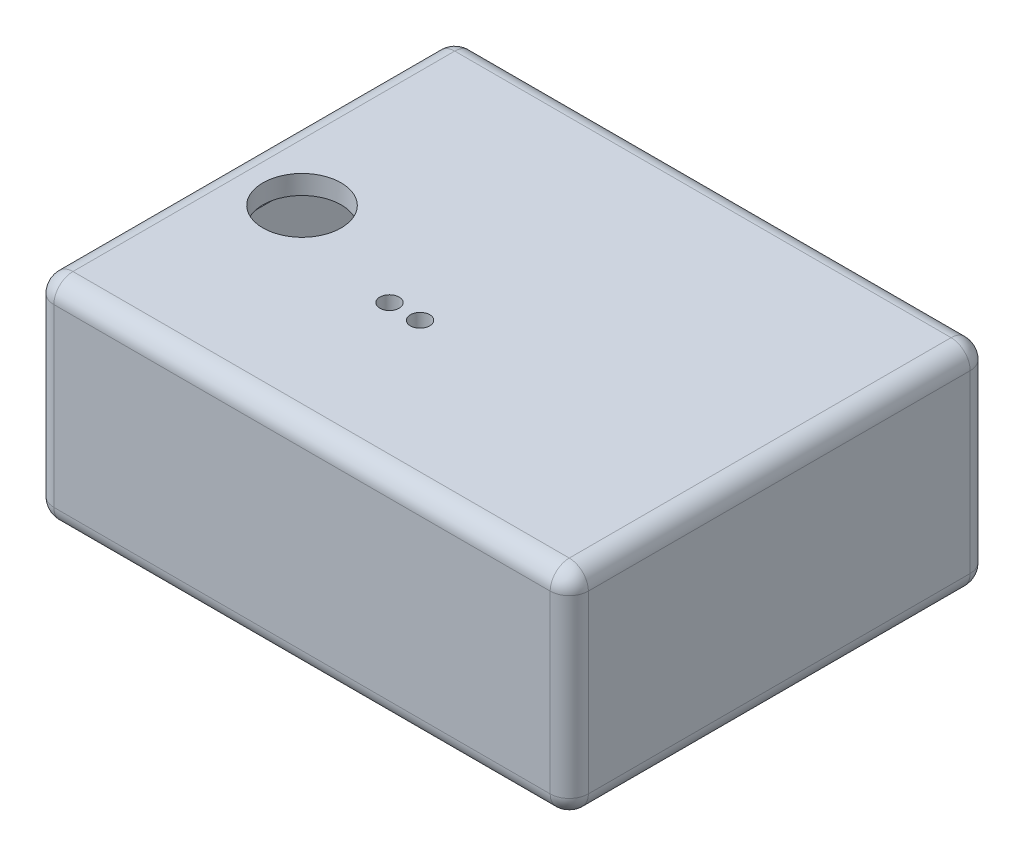
SolidWorks part; units mm, degrees
ref_plane "Front Plane" through (0, 0, 0) normal (0, 0, 1) x (1, 0, 0)
ref_plane "Top Plane" through (0, 0, 0) normal (0, 1, 0) x (1, 0, 0)
ref_plane "Right Plane" through (0, 0, 0) normal (1, 0, 0) x (0, 0, -1)
sketch "Sketch1" plane through (0, 0, 0) normal (0, 1, 0) x (1, 0, 0)
  line L1 (-70, -55) -> (70, -55)
  line L2 (-70, -55) -> (-70, 55)
  line L3 (-70, 55) -> (70, 55)
  line L4 (70, -55) -> (70, 55)
  line L5 (-70, -55) -> (70, 55) construction
  line L6 (-70, 55) -> (70, -55) construction
  point P0 (0, 0)
  dimension "D1" = 140
  dimension "D2" = 110
extrude "Boss-Extrude1" add sketch "Sketch1" along normal blind 56
sketch "Sketch2" plane through (0, 0, 0) normal (0, -1, 0) x (1, 0, 0)
  line L0 (-70, -55) -> (-70, 55) construction
  line L1 (-65, -50) -> (65, -50)
  line L2 (-65, -50) -> (-65, 50)
  line L3 (-65, 50) -> (65, 50)
  line L4 (65, -50) -> (65, 50)
  line L5 (-65, -50) -> (65, 50) construction
  line L6 (-65, 50) -> (65, -50) construction
  line L7 (-70, 55) -> (70, 55) construction
  point P0 (0, 0)
  dimension "D1" = 5
  dimension "D2" = 5
extrude "Cut-Extrude1" cut sketch "Sketch2" against normal blind 51
fillet "Fillet1" radius 5 4 edges at (0, 56, -55) (70, 56, 0) (0, 56, 55) (-70, 56, 0)
fillet "Fillet2" radius 5 8 edges at (-70, 25.5, -55) (70, 25.5, -55) (70, 25.5, 55) (-70, 25.5, 55) (-68.5355, 54.5355, -53.5355) (68.5355, 54.5355, -53.5355) (68.5355, 54.5355, 53.5355) (-68.5355, 54.5355, 53.5355)
fillet "Fillet3" radius 5 4 edges at (65, 51, 0) (0, 51, -50) (-65, 51, 0) (0, 51, 50)
fillet "Fillet4" radius 5 8 edges at (65, 23, 50) (65, 23, -50) (-65, 23, -50) (-65, 23, 50) (63.5355, 49.5355, 48.5355) (63.5355, 49.5355, -48.5355) (-63.5355, 49.5355, -48.5355) (-63.5355, 49.5355, 48.5355)
fillet "Fillet6" radius 5 8 edges at (-68.5355, 0, 53.5355) (-70, 0, 0) (-68.5355, 0, -53.5355) (0, 0, -55) (68.5355, 0, -53.5355) (70, 0, 0) (68.5355, 0, 53.5355) (0, 0, 55)
sketch "Sketch3" plane through (0, 56, 0) normal (0, 1, 0) x (1, 0, 0)
  line L0 (-70, -50) -> (-70, 50) construction
  line L1 (65, -55) -> (-65, -55) construction
  circle A0 centre (-16.48, -15.61) radius 2.54
  circle A1 centre (-8.48, -15.61) radius 2.54
  dimension "D1" = 8
  dimension "D2" = 53.52
  dimension "D3" = 39.39
extrude "Cut-Extrude2" cut sketch "Sketch3" against normal blind 5
sketch "Sketch4" plane through (0, 56, 0) normal (0, 1, 0) x (1, 0, 0)
  line L0 (-65, 50) -> (-65, -50) construction
  line L2 (65, -55) -> (-65, -55) construction
  circle A0 centre (-50, -5) radius 10.25
  point P4 (0, 0)
  point P7 (0, 0)
  dimension "D1" = 20.5
  dimension "D2" = 15
  dimension "D3" = 50
extrude "Cut-Extrude3" cut sketch "Sketch4" against normal blind 5
